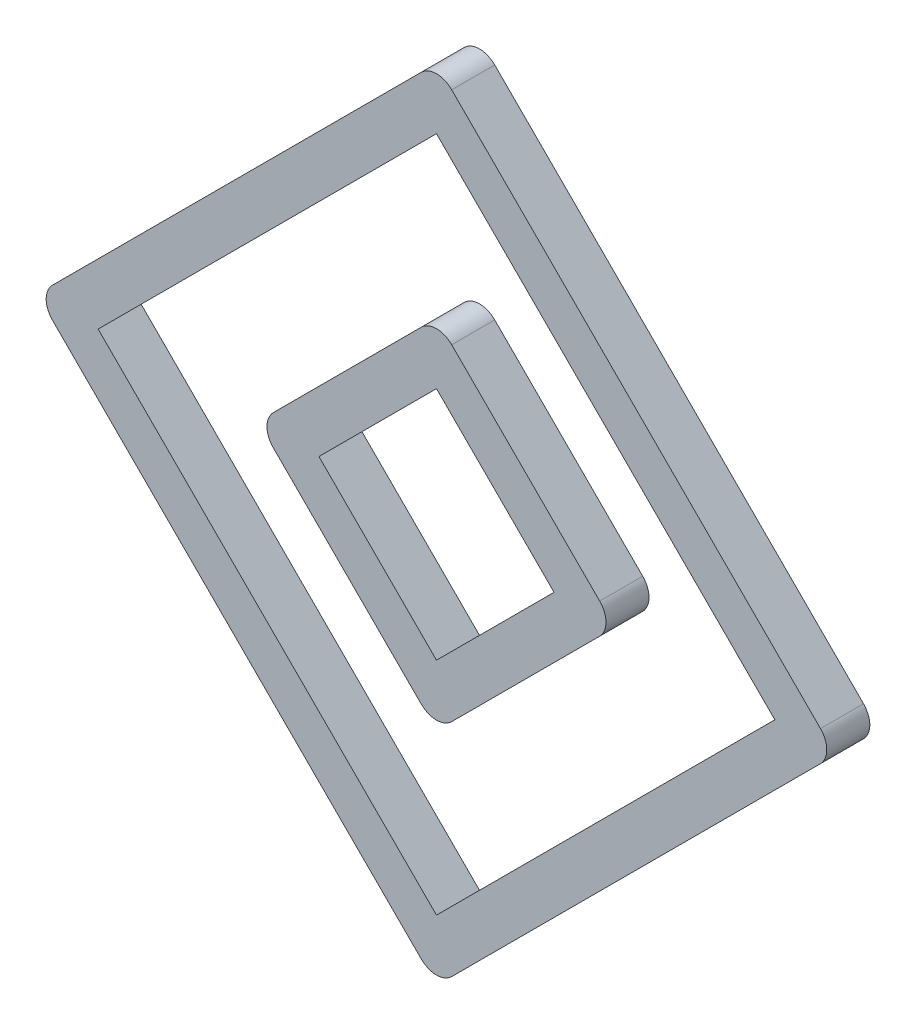
SolidWorks part; units mm, degrees
ref_plane "Front Plane" through (0, 0, 0) normal (0, 0, 1) x (1, 0, 0)
ref_plane "Top Plane" through (0, 0, 0) normal (0, 1, 0) x (1, 0, 0)
ref_plane "Right Plane" through (0, 0, 0) normal (1, 0, 0) x (0, 0, -1)
sketch "Sketch2" plane through (0, 0, 0) normal (0, 0, 1) x (1, 0, 0)
  line L34 (-37.3762, -135.6526) -> (-22.3762, -120.6526)
  line L35 (-23.6137, -119.4151) -> (-38.6137, -134.4151)
  line L36 (-37.3762, -135.6526) -> (-22.3762, -120.6526)
  line L37 (-23.6137, -119.4151) -> (-38.6137, -134.4151)
  line L38 (-28.396, -135.6526) -> (-22.3762, -129.6328)
  line L39 (-23.6137, -128.3954) -> (-29.6334, -134.4151)
  line L40 (-28.396, -135.6526) -> (-22.3762, -129.6328)
  line L41 (-23.6137, -128.3954) -> (-29.6334, -134.4151)
  line L42 (-22.3762, -140.4349) -> (-28.396, -134.4151)
  line L43 (-29.6334, -135.6526) -> (-23.6137, -141.6723)
  line L44 (-22.3762, -140.4349) -> (-28.396, -134.4151)
  line L45 (-29.6334, -135.6526) -> (-23.6137, -141.6723)
  line L46 (-22.3762, -141.6723) -> (-16.3565, -135.6526)
  line L47 (-17.5939, -134.4151) -> (-23.6137, -140.4349)
  line L48 (-22.3762, -141.6723) -> (-16.3565, -135.6526)
  line L49 (-17.5939, -134.4151) -> (-23.6137, -140.4349)
  line L50 (-8.6137, -134.4151) -> (-23.6137, -149.4151)
  line L51 (-22.3762, -150.6526) -> (-7.3762, -135.6526)
  line L52 (-8.6137, -134.4151) -> (-23.6137, -149.4151)
  line L53 (-22.3762, -150.6526) -> (-7.3762, -135.6526)
  line L54 (-38.6137, -135.6526) -> (-23.6137, -150.6526)
  line L55 (-22.3762, -149.4151) -> (-37.3762, -134.4151)
  line L56 (-38.6137, -135.6526) -> (-23.6137, -150.6526)
  line L57 (-22.3762, -149.4151) -> (-37.3762, -134.4151)
  line L58 (-23.6137, -120.6526) -> (-8.6137, -135.6526)
  line L59 (-7.3762, -134.4151) -> (-22.3762, -119.4151)
  line L60 (-23.6137, -120.6526) -> (-8.6137, -135.6526)
  line L61 (-7.3762, -134.4151) -> (-22.3762, -119.4151)
  line L62 (-16.3565, -134.4151) -> (-22.3762, -128.3954)
  line L63 (-23.6137, -129.6328) -> (-17.5939, -135.6526)
  line L64 (-16.3565, -134.4151) -> (-22.3762, -128.3954)
  line L65 (-23.6137, -129.6328) -> (-17.5939, -135.6526)
  arc A18 (-38.6137, -134.4151) -> (-37.3762, -135.6526) centre (-37.995, -135.0339) ccw
  arc A19 (-22.3762, -120.6526) -> (-23.6137, -119.4151) centre (-22.995, -120.0339) ccw
  arc A20 (-38.6137, -134.4151) -> (-37.3762, -135.6526) centre (-37.995, -135.0339) ccw
  arc A21 (-22.3762, -120.6526) -> (-23.6137, -119.4151) centre (-22.995, -120.0339) ccw
  arc A22 (-22.3762, -129.6328) -> (-23.6137, -128.3954) centre (-22.995, -129.0141) ccw
  arc A23 (-29.6334, -134.4151) -> (-28.396, -135.6526) centre (-29.0147, -135.0339) ccw
  arc A24 (-22.3762, -129.6328) -> (-23.6137, -128.3954) centre (-22.995, -129.0141) ccw
  arc A25 (-29.6334, -134.4151) -> (-28.396, -135.6526) centre (-29.0147, -135.0339) ccw
  arc A26 (-23.6137, -141.6723) -> (-22.3762, -140.4349) centre (-22.995, -141.0536) ccw
  arc A27 (-28.396, -134.4151) -> (-29.6334, -135.6526) centre (-29.0147, -135.0339) ccw
  arc A28 (-23.6137, -141.6723) -> (-22.3762, -140.4349) centre (-22.995, -141.0536) ccw
  arc A29 (-28.396, -134.4151) -> (-29.6334, -135.6526) centre (-29.0147, -135.0339) ccw
  arc A30 (-23.6137, -140.4349) -> (-22.3762, -141.6723) centre (-22.995, -141.0536) ccw
  arc A31 (-16.3565, -135.6526) -> (-17.5939, -134.4151) centre (-16.9752, -135.0339) ccw
  arc A32 (-23.6137, -140.4349) -> (-22.3762, -141.6723) centre (-22.995, -141.0536) ccw
  arc A33 (-16.3565, -135.6526) -> (-17.5939, -134.4151) centre (-16.9752, -135.0339) ccw
  arc A34 (-7.3762, -135.6526) -> (-8.6137, -134.4151) centre (-7.995, -135.0339) ccw
  arc A35 (-23.6137, -149.4151) -> (-22.3762, -150.6526) centre (-22.995, -150.0339) ccw
  arc A36 (-7.3762, -135.6526) -> (-8.6137, -134.4151) centre (-7.995, -135.0339) ccw
  arc A37 (-23.6137, -149.4151) -> (-22.3762, -150.6526) centre (-22.995, -150.0339) ccw
  arc A38 (-37.3762, -134.4151) -> (-38.6137, -135.6526) centre (-37.995, -135.0339) ccw
  arc A39 (-23.6137, -150.6526) -> (-22.3762, -149.4151) centre (-22.995, -150.0339) ccw
  arc A40 (-37.3762, -134.4151) -> (-38.6137, -135.6526) centre (-37.995, -135.0339) ccw
  arc A41 (-23.6137, -150.6526) -> (-22.3762, -149.4151) centre (-22.995, -150.0339) ccw
  arc A42 (-8.6137, -135.6526) -> (-7.3762, -134.4151) centre (-7.995, -135.0339) ccw
  arc A43 (-22.3762, -119.4151) -> (-23.6137, -120.6526) centre (-22.995, -120.0339) ccw
  arc A44 (-8.6137, -135.6526) -> (-7.3762, -134.4151) centre (-7.995, -135.0339) ccw
  arc A45 (-22.3762, -119.4151) -> (-23.6137, -120.6526) centre (-22.995, -120.0339) ccw
  arc A46 (-22.3762, -128.3954) -> (-23.6137, -129.6328) centre (-22.995, -129.0141) ccw
  arc A47 (-17.5939, -135.6526) -> (-16.3565, -134.4151) centre (-16.9752, -135.0339) ccw
  arc A48 (-22.3762, -128.3954) -> (-23.6137, -129.6328) centre (-22.995, -129.0141) ccw
  arc A49 (-17.5939, -135.6526) -> (-16.3565, -134.4151) centre (-16.9752, -135.0339) ccw
  dimension "D1" = 0
  dimension "D2" = 0
  dimension "D3" = 0
  dimension "D4" = 0
  dimension "D5" = 0
  dimension "D6" = 0
  dimension "D7" = 0
  dimension "D8" = 0
extrude "Boss-Extrude1" add sketch "Sketch2" against normal up to surface (1.75 mm away) contours A45 L37 A40 L57 L60 | A36 L61 A21 L36 L52 | A21 A45 L60 L36 | A44 L60 L57 A41 L53 | L60 A44 A36 L52 | A37 A41 L57 L52 | A37 L52 L36 A20 L56 | L57 A40 A20 L36 | A48 A29 L44 L40 L65 | A48 L65 L40 A24 | A33 A24 L40 L65 L49 | L65 A49 A33 L49 | A49 L65 L49 L44 A28 | L49 A32 A28 L44 | A32 L49 L44 L40 A25 | L44 A29 A25 L40 | L52 A37 L53 A36 | L60 A44 L61 A45 | L36 A21 L37 A20 | A40 L56 A41 L57 region at (-37.9335, -135.0339, 0) region at (-30.4996, -142.5385, 0) region at (-30.4996, -127.5293, 0) region at (-22.995, -120.0953, 0) region at (-15.4904, -127.5293, 0) region at (-22.995, -149.9724, 0) region at (-15.4904, -142.5385, 0) region at (-8.0564, -135.0339, 0) region at (-28.9533, -135.0339, 0) region at (-26.0178, -138.0567, 0) region at (-26.0178, -132.011, 0) region at (-22.995, -129.0756, 0) region at (-19.9721, -132.011, 0) region at (-19.9721, -138.0567, 0) region at (-22.995, -140.9922, 0) region at (-17.0367, -135.0339, 0)
